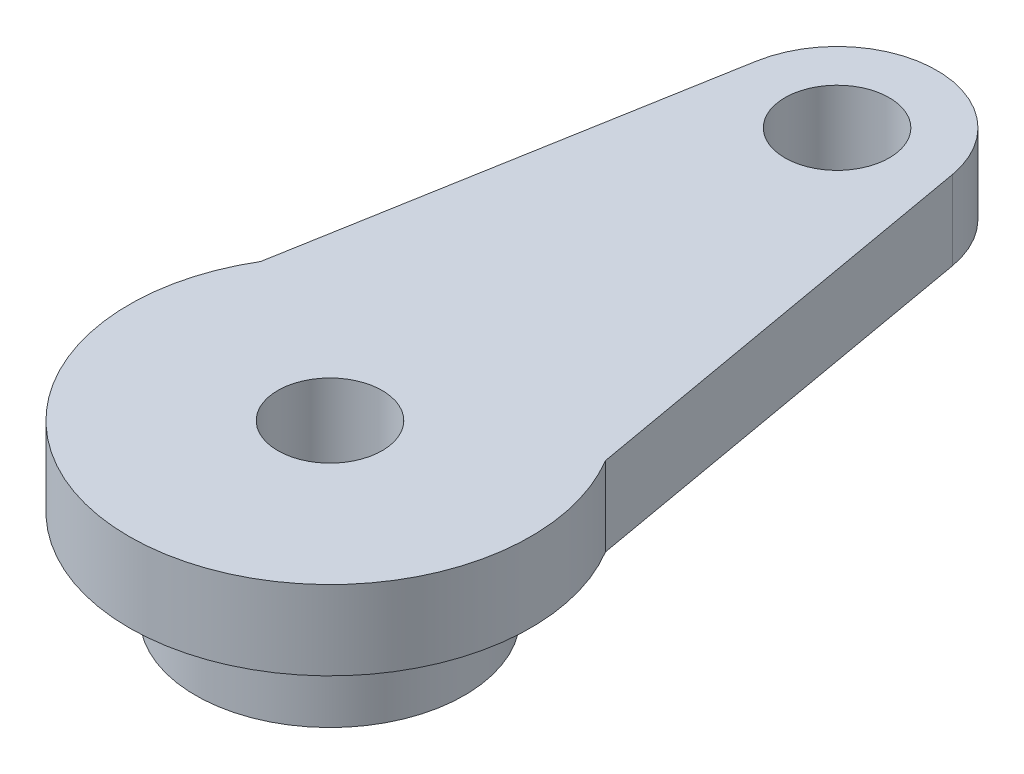
SolidWorks part; units mm, degrees
material "PC High Viscosity"
ref_plane "Front Plane" through (0, 0, 0) normal (0, 0, 1) x (1, 0, 0)
ref_plane "Top Plane" through (0, 0, 0) normal (0, 1, 0) x (1, 0, 0)
ref_plane "Right Plane" through (0, 0, 0) normal (1, 0, 0) x (0, 0, -1)
sketch "BaseS" plane through (0, 0, 0) normal (0, 1, 0) x (1, 0, 0)
  circle A0 centre (0, 0) radius 6.35
  dimension "D1" = 12.7
extrude "BASE" add sketch "BaseS" along normal blind 5.4
sketch "TopBoreS" plane through (0, 5.4, 0) normal (0, 1, 0) x (1, 0, 0)
  circle A0 centre (0, 0) radius 1.65
  dimension "D1" = 3.3
extrude "TOP BORE" cut sketch "TopBoreS" against normal through all
sketch "HornHalfS" plane through (0, 5.4, 0) normal (0, 1, 0) x (1, 0, 0)
  line L0 (0, 0) -> (0, 16.03) construction
  line L1 (-3.1021, 16.577) -> (-5.4507, 3.2577)
  line L2 (0, 19.18) -> (0, 16.03) construction
  line L3 (3.1021, 16.577) -> (5.4507, 3.2577)
  arc A0 (3.1021, 16.577) -> (-3.1021, 16.577) centre (0, 16.03) ccw
  arc A1 (5.4507, 3.2577) -> (-5.4507, 3.2577) centre (0, 0) ccw
  circle A2 centre (0, 0) radius 6.35 construction
  dimension "D1" = 6.3
  dimension "D2" = 19.18
  dimension "D3" = 10
  dimension "D4" = 10.9014
extrude "HORN HALF" add sketch "HornHalfS" against normal blind 2.5
sketch "HornAttachS" plane through (0, 5.4, 0) normal (0, 1, 0) x (1, 0, 0)
  circle A0 centre (0, 16.03) radius 1.65
  dimension "D1" = 3.3
extrude "HORN ATTACH" cut sketch "HornAttachS" against normal through all
sketch "HA LP RS" plane through (0, 0, 0) normal (0, 1, 0) x (1, 0, 0)
  line L0 (0, 0) -> (0, 16.03) construction
sketch "ToothS" plane through (0, 0, 0) normal (0, -1, 0) x (1, 0, 0)
  line L0 (0, -2.9) -> (0.2629, -2.5867)
  line L1 (0, -2.9) -> (-0.2629, -2.5867)
  line L2 (0, -2.6) -> (0, -2.9) construction
  line L3 (0, 0) -> (0, -2.6) construction
  arc A0 (-0.2629, -2.5867) -> (0.2629, -2.5867) centre (0, 0) ccw
  dimension "D1" = 5.2
  dimension "D2" = 80
  dimension "D3" = 0.3
extrude "TOOTH" [suppressed] cut sketch "ToothS" against normal blind 3
pattern_circular "TOOTH CP" [suppressed] count 26 over 360 of bodies 107
sketch "BottomBoreS" [suppressed] plane through (0, 0, 0) normal (0, -1, 0) x (-1, 0, 0)
  circle A0 centre (0, 0) radius 2.6
  arc A1 (0.2629, 2.5867) -> (-0.2629, 2.5867) centre (0, 0) ccw construction
extrude "BOTTOM BORE" [suppressed] cut sketch "BottomBoreS" against normal up to surface (3 mm away)
sketch "HoldingShaftS" plane through (0, 0, 0) normal (0, -1, 0) x (1, 0, 0)
  circle A0 centre (0, 0) radius 6.35 construction
  circle A1 centre (0, 0) radius 6.35
  circle A2 centre (0, 0) radius 4.25
  dimension "D1" = 2.1
  dimension "D2" = 8.5
extrude "HOLDING SHAFT" cut sketch "HoldingShaftS" against normal up to surface (2.9 mm away) up to face at (0, 2.9, -14.38)
sketch "RibS" plane through (0, 0, 0) normal (0, 0, 1) x (1, 0, 0)
  line L0 (4.21, 1) -> (5.8043, 2.9)
  line L1 (5.8043, 2.9) -> (4.21, 2.9)
  line L2 (4.21, 1) -> (4.16, 1)
  line L3 (4.16, 1) -> (4.16, 2.9)
  line L4 (4.21, 1) -> (4.21, 2.9) construction
  line L5 (4.16, 2.9) -> (4.21, 2.9)
  line L6 (-4.25, 2.9) -> (4.25, 2.9) construction
  line L7 (4.21, 2.9) -> (4.25, 2.9) construction
  line L8 (4.25, 0) -> (4.25, 2.9) construction
  dimension "D1" = 1.9
  dimension "D2" = 0.05
  dimension "D3" = 40
  dimension "D4" = 0.09
extrude "RIB" [suppressed] add sketch "RibS" along normal mid plane 1
pattern_circular "RIB CP" [suppressed] count 4 over 360 of bodies 111
sketch "Sketch1" plane through (0, 5.4, 0) normal (0, 1, 0) x (1, 0, 0)
  circle A0 centre (0, 0) radius 2.875
  dimension "D1" = 5.75
extrude "Cut-Extrude1" [suppressed] cut sketch "Sketch1" against normal blind 1
ref_point "Point1"
ref_point "Point2" [suppressed]
ref_axis "Axis1" [suppressed] through (0, 5.4, 0) along (0, 0, -1)
sketch "Sketch3" plane through (0, 0, 0) normal (0, -1, 0) x (1, 0, 0)
  circle A0 centre (0, 0) radius 3.025
  dimension "D1" = 6.05
extrude "Cut-Extrude2" cut sketch "Sketch3" against normal up to surface (2.9 mm away) up to face at (0, 2.9, -14.38)
